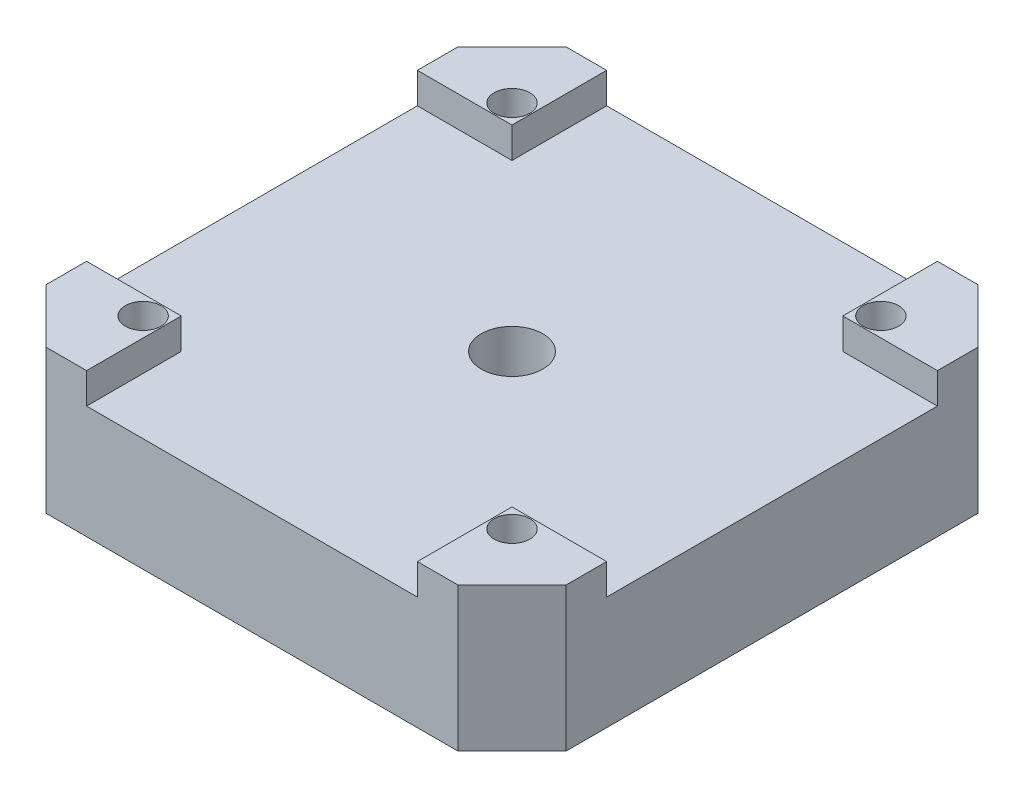
SolidWorks part; units mm, degrees
material "Alumina"
ref_plane "Front Plane" through (0, 0, 0) normal (0, 0, 1) x (1, 0, 0)
ref_plane "Top Plane" through (0, 0, 0) normal (0, 1, 0) x (1, 0, 0)
ref_plane "Right Plane" through (0, 0, 0) normal (1, 0, 0) x (0, 0, -1)
sketch "Sketch1" plane through (0, 0, 0) normal (0, 1, 0) x (1, 0, 0)
  line L0 (-21.15, 16.7509) -> (-16.7509, 21.15)
  line L1 (-16.7509, -21.15) -> (16.7509, -21.15)
  line L2 (-21.15, -16.7509) -> (-21.15, 16.7509)
  line L3 (-16.7509, 21.15) -> (16.7509, 21.15)
  line L4 (21.15, -16.7509) -> (21.15, 16.7509)
  line L7 (16.7509, 21.15) -> (21.15, 16.7509)
  line L8 (16.7509, -21.15) -> (21.15, -16.7509)
  line L9 (-21.15, -16.7509) -> (-16.7509, -21.15)
  point P0 (0, 0)
  dimension "D1" = 42.3
  dimension "D2" = 42.3
  dimension "D3" = 53.6
  dimension "D4" = 45
  dimension "D5" = 45
  dimension "D7" = 53.6
extrude "Boss-Extrude1" add sketch "Sketch1" along normal blind 11.7
sketch "Sketch12" plane through (21.15, 0, 0) normal (1, 0, 0) x (0, 0, -1)
  line L0 (-13.4509, 11.7) -> (-13.4509, 9.2)
  line L1 (-16.7509, 11.7) -> (16.7509, 11.7) construction
  line L2 (-13.4509, 9.2) -> (13.4509, 9.2)
  line L3 (13.4509, 9.2) -> (13.4509, 11.7)
  line L4 (13.4509, 11.7) -> (-13.4509, 11.7)
  dimension "D1" = 2.5
  dimension "D2" = 3.3
  dimension "D3" = 3.3
extrude "Cut-Extrude6" cut sketch "Sketch12" against normal through all
sketch "Sketch13" plane through (0, 0, 21.15) normal (0, 0, 1) x (1, 0, 0)
  line L0 (-13.4509, 11.7) -> (-13.4509, 9.2)
  line L1 (-16.7509, 11.7) -> (16.7509, 11.7) construction
  line L2 (-13.4509, 9.2) -> (13.4509, 9.2)
  line L3 (13.4509, 9.2) -> (13.4509, 11.7)
  line L4 (13.4509, 11.7) -> (-13.4509, 11.7)
  dimension "D1" = 3.3
  dimension "D2" = 3.3
  dimension "D3" = 2.5
extrude "Cut-Extrude7" cut sketch "Sketch13" against normal through all
sketch "Sketch14" plane through (0, 0, 0) normal (0, -1, 0) x (1, 0, 0)
  circle A0 centre (0, 0) radius 3.25
  dimension "D1" = 6.5
extrude "Cut-Extrude8" cut sketch "Sketch14" against normal blind 3
sketch "Sketch15" plane through (0, 3, 0) normal (0, -1, 0) x (1, 0, 0)
  circle A0 centre (0, 0) radius 2.5
  dimension "D1" = 5
extrude "Cut-Extrude9" cut sketch "Sketch15" against normal through all
hole_wizard "CBORE for M2.5 Pan Head Machine Screw1" positions "Sketch17" profile "Sketch16" counterbore size "M2.5" standard "ANSI Metric" end condition through all
sketch "Sketch17" plane through (0, 0, 0) normal (0, -1, 0) x (-1, 0, 0)
  point P0 (15, -15)
  point P2 (-15, -15)
  point P4 (-15, 15)
  point P6 (15, 15)
  dimension "D1" = 30
  dimension "D2" = 30
  dimension "D3" = 30
  dimension "D4" = 30
  dimension "D5" = 6.15
  dimension "D6" = 6.15
  dimension "D7" = 6.15
  dimension "D8" = 6.15
sketch "Sketch16" plane through (-15, 0, 15) normal (1, 0, 0) x (0, 0, -1)
  line L0 (0, 0) -> (0, 11.7)
  line L1 (0, 11.7) -> (1.45, 11.7)
  line L3 (1.45, 11.7) -> (1.45, 2.1)
  line L4 (1.45, 2.1) -> (3, 2.1)
  line L5 (3, 2.1) -> (3, 0)
  line L7 (3, 0) -> (0, 0)
  line L11 (0, -6.35) -> (0, 107.95) construction
  dimension "Thru Hole Dia." = 2.9
  dimension "Thru Hole Depth" = 11.7
  dimension "C'Bore Dia." = 6
  dimension "C'Bore Depth" = 2.1
